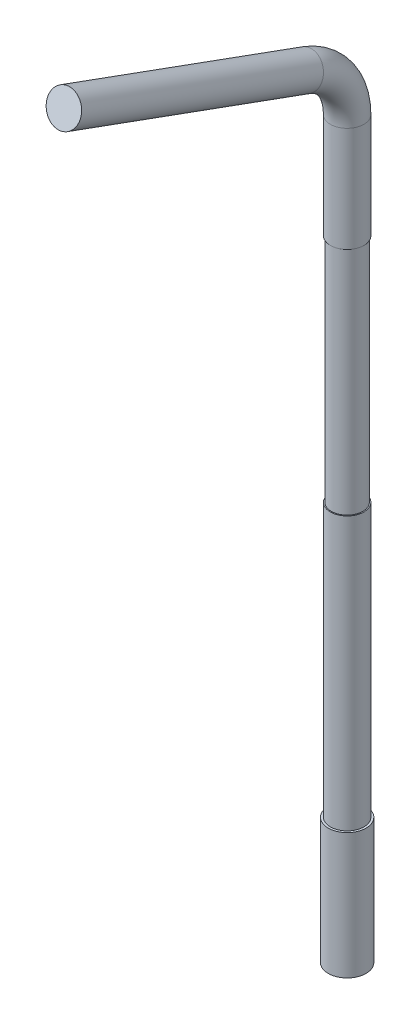
SolidWorks part; units mm, degrees
material "Stainless Steel (ferritic)"
ref_plane "Front Plane" through (0, 0, 0) normal (0, 0, 1) x (1, 0, 0)
ref_plane "Top Plane" through (0, 0, 0) normal (0, 1, 0) x (1, 0, 0)
ref_plane "Right Plane" through (0, 0, 0) normal (1, 0, 0) x (0, 0, -1)
sketch "Sketch1" plane through (0, 0, 0) normal (1, 0, 0) x (0, 0, -1)
  line L0 (4.5, 0) -> (4.5, 35)
  line L1 (55, 0) -> (-55, 0) construction
  line L2 (2.5261, 37.8191) -> (-9, 42.0142)
  line L4 (0, 55) -> (0, -55) construction
  arc A0 (4.5, 35) -> (2.5261, 37.8191) centre (1.5, 35) ccw
  dimension "D1" = 3
  dimension "D2" = 4.5
  dimension "D3" = 35
  dimension "D4" = 13.5
  dimension "D5" = 70
sketch "Sketch2" plane through (0, 0, 0) normal (0, 1, 0) x (1, 0, 0)
  circle A0 centre (0, 4.5) radius 0.8
  dimension "D1" = 1.6
sweep "Sweep1" add profiles "Sketch2" path "Sketch1"
sketch "Sketch4" plane through (0, 0, 0) normal (0, 1, 0) x (1, 0, 0)
  circle A0 centre (0, 4.5) radius 0.9
  dimension "D1" = 1.8
extrude "Extrude1" add sketch "Sketch4" along normal blind 6
ref_plane "Plane1" through (0, 19, 0) normal (0, 1, 0) x (-1, 0, 0)
sketch "Sketch5" plane through (0, 19, 0) normal (0, 1, 0) x (-1, 0, 0)
  circle A0 centre (0, -4.5) radius 0.75
  dimension "D1" = 1.5
extrude "Extrude3" cut sketch "Sketch5" along normal blind 11 flip side to cut
ref_axis "Axis1" through (0, 30, -4.5) along (0, -1, 0)
